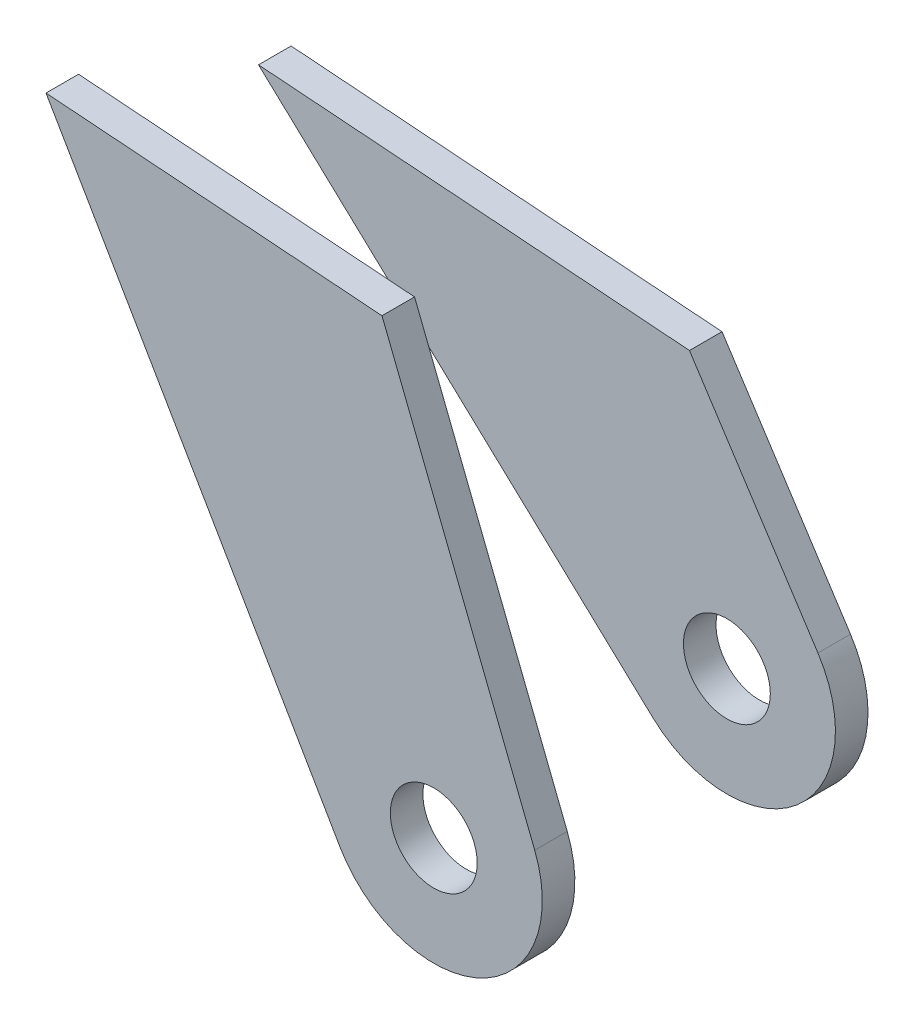
SolidWorks part; units mm, degrees
note: The reader was unsure of these and kept them because the rebuilt part matched: shared geometry of "3DSketch1<3>".
ref_plane "Front Plane" through (0, 0, 0) normal (0, 0, 1) x (1, 0, 0)
ref_plane "Top Plane" through (0, 0, 0) normal (0, 1, 0) x (1, 0, 0)
ref_plane "Right Plane" through (0, 0, 0) normal (1, 0, 0) x (0, 0, -1)
sketch3d "3DSketch1"
  line L0 (246, -2201, 222) -> (246, -2201, 234) construction
  line L1 (246, -2201, 222) -> (246, -2201, 210) construction
  line L2 (239.175, -2208.3089, 210) -> (202.8579, -2174.396, 210)
  line L3 (202.8579, -2174.396, 210) -> (242.5535, -2177.3364, 210)
  line L4 (242.5535, -2177.3364, 210) -> (254.3861, -2195.5527, 210)
  line L6 (210.2849, -2159.4329, 234) -> (241.2301, -2161.7252, 234)
  line L8 (230, -2115, 305) -> (220, -2250, 95) construction
  line L9 (230, -2115, 305) -> (220, -2250, 95) construction
  line L10 (242, -2201, 234) -> (250, -2201, 234) construction
  line L11 (237.3534, -2206.0236, 234) -> (210.2849, -2159.4329, 234)
  line L12 (246, -2205, 234) -> (246, -2197, 234) construction
  line L13 (239.175, -2208.3089, 210) -> (254.3861, -2195.5527, 210) construction
  line L14 (255.3, -2197.3244, 234) -> (241.2301, -2161.7252, 234)
  line L15 (237.3534, -2206.0236, 234) -> (255.3, -2197.3244, 234) construction
  line L16 (246, -2197, 210) -> (246, -2205, 210) construction
  line L17 (242, -2201, 210) -> (250, -2201, 210) construction
  circle A0 centre (246, -2201, 210) radius 4
  arc A1 (239.175, -2208.3089, 210) -> (254.3861, -2195.5527, 210) centre (246, -2201, 210) ccw
  circle A2 centre (246, -2201, 234) radius 4
  arc A3 (237.3534, -2206.0236, 234) -> (255.3, -2197.3244, 234) centre (246, -2201, 234) ccw
  point P0 (246, -2201, 222)
  point P8 (246, -2201, 220)
  point P13 (246, -2201, 214)
  point P16 (225.4762, -2176.0714, 210)
  point P19 (246, -2201, 238)
  point P20 (246, -2201, 244)
  point P28 (226.619, -2160.6429, 234)
  point P32 (0, 0, 0)
  point P33 (0, 0, 0)
  point P34 (0, 0, 0)
  point P35 (236.3034, -2208.566, 210)
  point P38 (236.0043, -2167.288, 210)
  point P39 (232.8881, -2163.582, 210)
  point P40 (216.8807, -2187.4554, 210)
  point P41 (234.5998, -2165.281, 210)
  point P42 (0, 0, 0)
  point P43 (236.1016, -2167.4581, 210)
  point P44 (0, 0, 0)
  point P45 (0, 0, 0)
  point P46 (0, 0, 0)
  point P47 (0, 0, 0)
  point P48 (0, 0, 0)
  point P49 (0, 0, 0)
  point P50 (0, 0, 0)
  point P51 (0, 0, 0)
  point P52 (0, 0, 0)
  point P53 (237.9109, -2153.3271, 234)
  point P54 (225.0728, -2159.1783, 234)
  point P55 (223.5394, -2156.0409, 234)
  point P56 (0, 0, 0)
  point P57 (0, 0, 0)
  point P58 (223.0432, -2155.0258, 234)
  point P59 (0, 0, 0)
  point P60 (0, 0, 0)
  point P61 (214.9779, -2166.9193, 210)
  point P62 (174.4195, -2147.8403, 210)
  point P63 (203.9294, -2175.3966, 210)
  point P64 (0, 0, 0)
  point P65 (0, 0, 0)
  point P66 (0, 0, 0)
  point P67 (0, 0, 0)
  point P68 (0, 0, 0)
  point P69 (0, 0, 0)
  dimension "D1" = 8
  dimension "D2" = 6
  dimension "D3" = 6
extrude "Boss-Extrude1" add sketch "3DSketch1" along a picked direction on the side against the normal blind 3 contours L11 L6 L14 A3 | A2
extrude "Boss-Extrude2" add sketch "3DSketch1<3>" along a picked direction on the side of the normal blind 3
sketch3d "3DSketch1<3>" same geometry as "3DSketch1"
